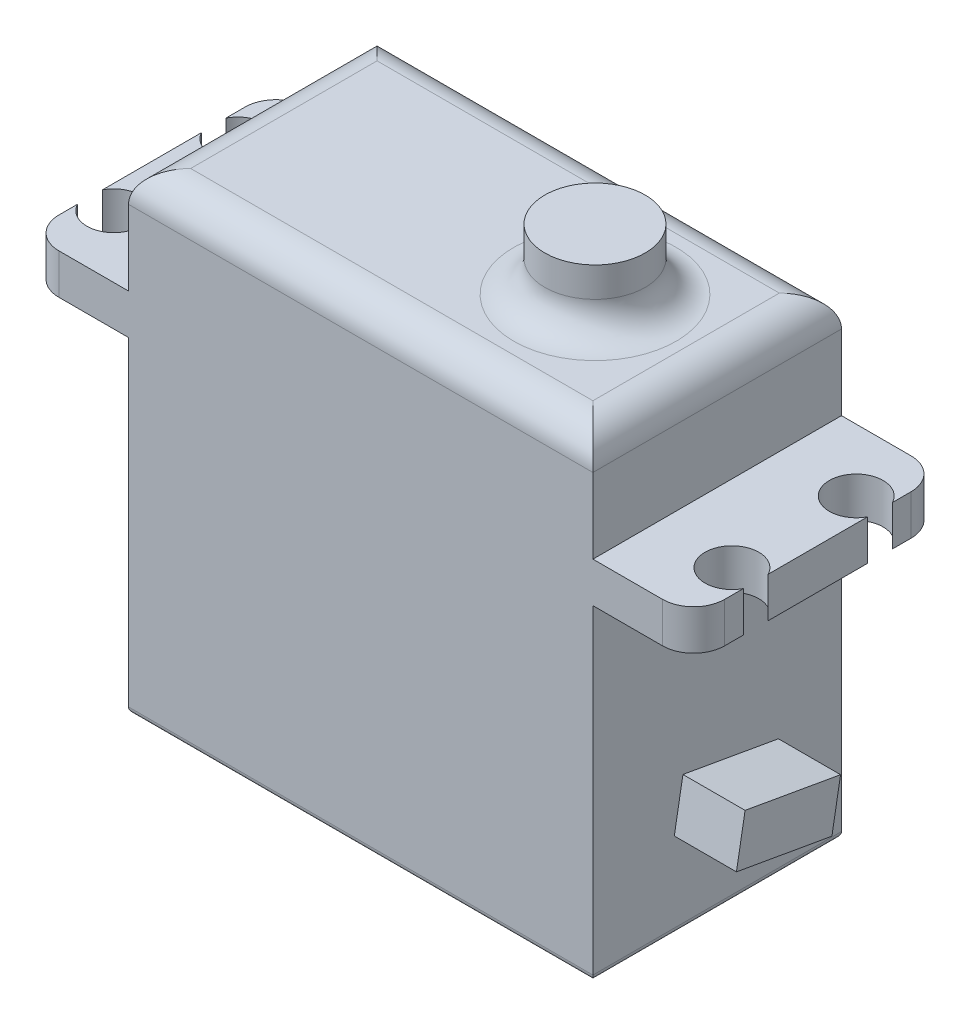
SolidWorks part; units mm, degrees
note: The reader was unsure of these and kept them because the rebuilt part matched: shared geometry of "Sketch1<5>", "Sketch1<6>".
ref_plane "前视基准面" through (0, 0, 0) normal (0, 0, 1) x (1, 0, 0)
ref_plane "上视基准面" through (0, 0, 0) normal (0, 1, 0) x (1, 0, 0)
ref_plane "右视基准面" through (0, 0, 0) normal (1, 0, 0) x (0, 0, -1)
sketch "Sketch1" plane through (0, 0, 0) normal (0, 1, 0) x (1, 0, 0)
  line L0 (27.25, 6) -> (27.25, 7.5)
  line L1 (-23.8196, -10) -> (24.75, -10)
  line L2 (-26.3196, -7.5) -> (-26.3196, -6)
  line L3 (-23.8521, 10) -> (24.75, 10)
  line L4 (27.25, -7.5) -> (27.25, -6)
  line L5 (-27.25, -10) -> (27.25, 10) construction
  line L6 (-27.25, 10) -> (27.25, -10) construction
  line L7 (27.25, -4) -> (27.25, 4)
  line L8 (-26.3196, -4) -> (-26.3196, 3.969)
  line L9 (-26.3521, 7.5) -> (-26.3521, 5.9687)
  line L10 (-18.2196, 10) -> (-18.2196, -10)
  line L11 (-18.2196, -10) -> (-18.2196, 10)
  line L12 (19.15, 10) -> (19.15, -10)
  line L13 (19.15, -10) -> (19.15, 10)
  line L14 (-19.15, -90.7625) -> (-19.15, -110.7625)
  line L15 (-24.75, -90.7625) -> (24.75, -90.7625)
  line L16 (-27.25, -93.2625) -> (-27.25, -94.7625)
  line L17 (-24.75, -110.7625) -> (24.75, -110.7625)
  line L18 (27.25, -93.2625) -> (27.25, -94.7625)
  line L19 (27.25, -106.7625) -> (27.25, -108.2625)
  line L20 (19.15, -90.7625) -> (19.15, -110.7625)
  line L21 (27.25, -96.7625) -> (27.25, -104.7625)
  line L22 (-27.25, -106.7625) -> (-27.25, -108.2625)
  line L23 (-27.25, -96.7625) -> (-27.25, -104.7625)
  line L25 (-19.15, -90.7625) -> (19.15, -90.7625)
  line L26 (-19.15, -90.7625) -> (-19.15, -110.7625)
  line L27 (-19.15, -110.7625) -> (19.15, -110.7625)
  line L28 (19.15, -90.7625) -> (19.15, -110.7625)
  arc A0 (27.25, -6) -> (27.25, -4) centre (25.3354, -5) cw
  arc A1 (27.25, -94.7625) -> (27.25, -96.7625) centre (25.3354, -95.7625) ccw
  arc A2 (-26.3196, -4) -> (-26.3196, -6) centre (-24.405, -5) cw
  arc A3 (27.25, 4) -> (27.25, 6) centre (25.3354, 5) cw
  arc A4 (-23.8521, 10) -> (-26.3521, 7.5) centre (-23.8521, 7.5) ccw
  arc A5 (27.25, 7.5) -> (24.75, 10) centre (24.75, 7.5) ccw
  arc A6 (24.75, -10) -> (27.25, -7.5) centre (24.75, -7.5) ccw
  arc A7 (-26.3196, -7.5) -> (-23.8196, -10) centre (-23.8196, -7.5) ccw
  arc A8 (-26.3521, 5.9687) -> (-26.3196, 3.969) centre (-24.4215, 5) cw
  arc A9 (27.25, -104.7625) -> (27.25, -106.7625) centre (25.3354, -105.7625) ccw
  arc A10 (27.25, -93.2625) -> (24.75, -90.7625) centre (24.75, -93.2625) ccw
  arc A11 (24.75, -110.7625) -> (27.25, -108.2625) centre (24.75, -108.2625) ccw
  arc A12 (-24.75, -110.7625) -> (-27.25, -108.2625) centre (-24.75, -108.2625) cw
  arc A13 (-24.75, -90.7625) -> (-27.25, -93.2625) centre (-24.75, -93.2625) ccw
  arc A14 (-27.25, -94.7625) -> (-27.25, -96.7625) centre (-25.3354, -95.7625) cw
  arc A15 (-27.25, -104.7625) -> (-27.25, -106.7625) centre (-25.3354, -105.7625) cw
  point P6 (-23.0194, 35.6443)
  point P7 (-28.2176, 31.4543)
  point P12 (-23.0194, 35.6443)
  point P27 (-26.3521, 5.9687)
  point P28 (23.1754, -5)
  point P61 (27.25, -90.7625)
  point P64 (27.25, -110.7625)
  point P69 (-27.25, -90.7625)
  dimension "D4" = 15
  dimension "D7" = 2.16
  dimension "D8" = 2.16
  dimension "D11" = 2.5
  dimension "D12" = 8.1
  dimension "D13" = 2.5
  dimension "D14" = 2.5
  dimension "D6" = 2.16
  dimension "D9" = 2.16
  dimension "D16" = 2.5
  dimension "D17" = 2
  dimension "D18" = 54.5
  dimension "D22" = 2.16
  dimension "D25" = 5
  dimension "D27" = 2.16
  dimension "D28" = 2.5
  dimension "D29" = 2.5
  dimension "D30" = 2.5
  dimension "D31" = 2.5
  dimension "D32" = 2.16
  dimension "D35" = 2.16
  dimension "D1" = 20
  dimension "D2" = 54.5
  dimension "D5" = 2
  dimension "D10" = 10
  dimension "D15" = 8.1
  dimension "D19" = 20
  dimension "D20" = 8.1
  dimension "D21" = 8.1
  dimension "D23" = 2
  dimension "D24" = 5
  dimension "D26" = 10
  dimension "D33" = 2
  dimension "D34" = 5
  dimension "D36" = 2
  dimension "D37" = 10
  dimension "D38" = 15
  dimension "D39" = 2
  dimension "D40" = 15
  dimension "D41" = 2
extrude "Boss-Extrude2" add sketch "Sketch1" along normal blind 3.24 contours L9 A8 L8 A2 L2 A7 L1 L10 L3 A4 | L1 A6 L4 A0 L7 A3 L0 A5 L3 L12
extrude "Boss-Extrude3" add sketch "Sketch1<5>" along normal blind 11.78 contours L12 L3 L10 L1
sketch "Sketch1<5>" plane through (0, 0, 0) normal (0, 1, 0) x (1, 0, 0) same geometry as "Sketch1"
sketch "Sketch2" plane through (0, 11.78, 0) normal (0, 1, 0) x (1, 0, 0)
  circle A0 centre (9.3165, 0) radius 4.04
  point P3 (0, 0)
  dimension "D1" = 8.08
  dimension "D2" = 9.3165
extrude "Boss-Extrude4" add sketch "Sketch2" along normal blind 4.9
sketch "Sketch3" plane through (0, 16.68, 0) normal (0, 1, 0) x (1, 0, 0)
  line L0 (-18.2196, 10) -> (19.15, 10) construction
  line L1 (-18.2196, -10) -> (19.15, -10) construction
  line L2 (2.9354, 7.992) -> (5.7005, 9.5181)
  line L3 (5.7005, 9.5181) -> (2.9354, 7.992)
  line L4 (19.15, 10) -> (19.15, -10) construction
  line L5 (4.3179, 8.7551) -> (5.7434, 6.1723)
  line L6 (5.7434, 6.1723) -> (4.3179, 8.7551)
  line L7 (4.3179, 8.7551) -> (5.7434, 6.1723)
  line L8 (15.3223, 3.4066) -> (17.9051, 4.8321)
  line L9 (17.9051, 4.8321) -> (15.3223, 3.4066)
  line L10 (15.3223, 3.4066) -> (17.9051, 4.8321)
  line L11 (13.5666, 12.6927) -> (22.2435, -3.0286)
  line L12 (22.2435, -3.0286) -> (13.5666, 12.6927)
  line L13 (12.5566, -6.1723) -> (13.9821, -8.7551)
  line L14 (13.9821, -8.7551) -> (12.5566, -6.1723)
  line L15 (8.1146, -11.9934) -> (19.8495, -5.5167)
  line L16 (19.8495, -5.5167) -> (8.1146, -11.9934)
  line L17 (0.3949, -4.8321) -> (2.9777, -3.4066)
  line L18 (2.9777, -3.4066) -> (0.3949, -4.8321)
  line L19 (5.0887, -13.3366) -> (-4.2989, 3.6725)
  line L20 (-4.2989, 3.6725) -> (5.0887, -13.3366)
  circle A0 centre (9.15, 0) radius 10
  circle A1 centre (5.7434, 6.1723) radius 1.17
  circle A2 centre (2.9777, -3.4066) radius 1.17
  circle A3 centre (12.5566, -6.1723) radius 1.17
  circle A4 centre (15.3223, 3.4066) radius 1.17
  circle A5 centre (9.15, 0) radius 1.17
  point P3 (17.9051, 4.8321)
  point P6 (4.3179, 8.7551)
  point P9 (0.3949, -4.8321)
  point P11 (13.9821, -8.7551)
  point P15 (9.15, 0)
  point P18 (16.3467, 3.972)
  point P20 (5.178, 7.1967)
  point P27 (4.3179, 8.7551)
  point P32 (17.9051, 4.8321)
  point P36 (13.9821, -8.7551)
  point P37 (13.122, -7.1967)
  point P38 (1.9533, -3.972)
  point P41 (0.3949, -4.8321)
  dimension "D1" = 20
  dimension "D2" = 2.34
  dimension "D3" = 2.34
  dimension "D4" = 2.34
  dimension "D5" = 2.34
  dimension "D6" = 2.34
  dimension "D7" = 1.78
  dimension "D8" = 1.78
  dimension "D9" = 1.78
  dimension "D10" = 1.78
  dimension "D11" = 7.05
  dimension "D12" = 10
fillet "Fillet5" radius 2.5 5 edges at (0.4652, 11.78, 10) (-18.2196, 11.78, 0) (0.4652, 11.78, -10) (19.15, 11.78, 0) (9.3165, 11.78, 4.04)
extrude "Boss-Extrude8" add sketch "Sketch1<6>" against normal blind 16.74 contours L12 L3 L10 L1
sketch "Sketch1<6>" plane through (0, 0, 0) normal (0, 1, 0) x (1, 0, 0) same geometry as "Sketch1"
sketch "Sketch6" plane through (19.15, 0, 0) normal (1, 0, 0) x (0, 0, -1)
  line L0 (10, -16.74) -> (-10, -16.74) construction
  line L1 (-2.7574, -15.3855) -> (4.9241, -16.74)
  line L2 (-2.7574, -15.3855) -> (-3.452, -19.3248)
  line L3 (-3.452, -19.3248) -> (4.2295, -20.6792)
  line L4 (4.9241, -16.74) -> (4.2295, -20.6792)
  point P11 (0.7013, -18.2293)
  dimension "D1" = 7.8
  dimension "D2" = 4
extrude "Boss-Extrude9" add sketch "Sketch6" along normal blind 5
sketch "Sketch7" plane through (0, -16.74, 0) normal (0, -1, 0) x (1, 0, 0)
  line L1 (-18.2196, 10) -> (19.15, 10)
  line L2 (-18.2196, 10) -> (-18.2196, -10)
  line L3 (-18.2196, -10) -> (19.15, -10)
  line L4 (19.15, 10) -> (19.15, -10)
extrude "Boss-Extrude10" add sketch "Sketch7" along normal blind 9.5
fillet "Fillet6" radius 0.5 4 edges at (0.4652, -26.24, 10) (19.15, -26.24, 0) (0.4652, -26.24, -10) (-18.2196, -26.24, 0)
sketch "Sketch8" plane through (0, -26.24, 0) normal (0, -1, 0) x (1, 0, 0)
  line L0 (16.22, 7.07) -> (16.22, 9.5)
  line L1 (18.65, 9.5) -> (-17.7196, 9.5) construction
  line L2 (16.22, 7.07) -> (18.65, 7.07) construction
  line L3 (18.65, -9.5) -> (18.65, 9.5) construction
  line L4 (16.22, -7.07) -> (16.22, -9.5) construction
  line L5 (-17.7196, -9.5) -> (18.65, -9.5) construction
  line L6 (16.22, -7.07) -> (18.65, -7.07) construction
  line L7 (-15.2896, -7.07) -> (-15.2896, -9.5) construction
  line L8 (-15.2896, -7.07) -> (-17.7196, -7.07) construction
  line L9 (-17.7196, 9.5) -> (-17.7196, -9.5) construction
  line L10 (-15.2896, 7.07) -> (-15.2896, 9.5) construction
  line L11 (-15.2896, 7.07) -> (-17.7196, 7.07) construction
  line L12 (-13.2596, 9.5) -> (-13.2596, 7.07)
  line L13 (-15.2896, 5.04) -> (-17.7196, 5.04)
  line L14 (14.19, 9.5) -> (14.19, 7.07)
  line L15 (16.22, 5.04) -> (18.65, 5.04)
  line L16 (14.19, -9.5) -> (14.19, -7.07)
  line L17 (16.22, -5.04) -> (18.65, -5.04)
  line L18 (-13.2596, -9.5) -> (-13.2596, -7.07)
  line L19 (-15.2896, -5.04) -> (-17.7196, -5.04)
  circle A0 centre (16.22, 7.07) radius 2.03
  circle A1 centre (16.22, -7.07) radius 2.03
  circle A2 centre (-15.2896, -7.07) radius 2.03
  circle A3 centre (-15.2896, 7.07) radius 2.03
  point P4 (16.22, 9.1)
  point P7 (18.25, 7.07)
  point P16 (16.22, -9.1)
  point P20 (18.25, -7.07)
  point P23 (-17.3196, -7.07)
  point P24 (-15.2896, -9.1)
  point P28 (-17.3196, 7.07)
  point P31 (-15.2896, 9.1)
  point P34 (-16.2984, 5.04)
  point P36 (-13.2596, 7.07)
  point P37 (-13.2596, 8.285)
  point P38 (-13.2596, 7.07)
  point P39 (14.19, 7.07)
  point P44 (16.22, 5.04)
  point P45 (14.19, 7.07)
  point P49 (16.22, -5.04)
  point P51 (14.19, -7.07)
  point P52 (14.19, -7.07)
  point P53 (16.22, -5.04)
  point P57 (-16.2187, -5.04)
  point P59 (-13.2596, -7.07)
  dimension "D1" = 4.06
  dimension "D2" = 4.06
  dimension "D3" = 4.06
  dimension "D4" = 4.06
  dimension "D11" = 0.4
  dimension "D5" = 0.4
  dimension "D6" = 0.4
  dimension "D7" = 0.4
  dimension "D8" = 0.4
  dimension "D9" = 0.4
  dimension "D10" = 0.4
  dimension "D12" = 0.4
extrude "Cut-Extrude2" cut sketch "Sketch8" against normal blind 1.66
